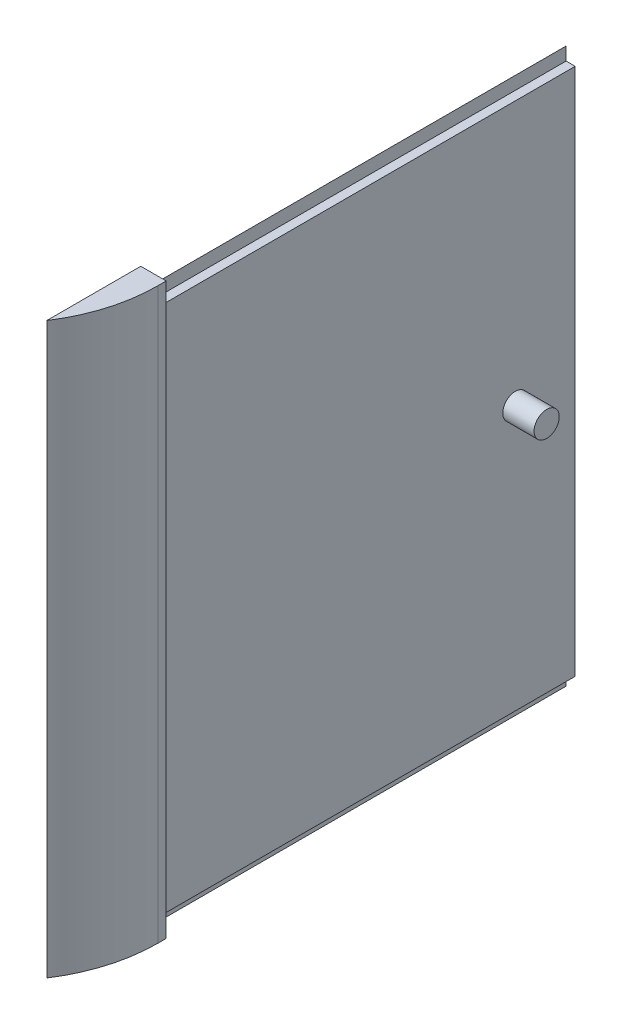
SolidWorks part; units mm, degrees
ref_plane "Front Plane" through (0, 0, 0) normal (0, 0, 1) x (1, 0, 0)
ref_plane "Top Plane" through (0, 0, 0) normal (0, 1, 0) x (1, 0, 0)
ref_plane "Right Plane" through (0, 0, 0) normal (1, 0, 0) x (0, 0, -1)
sketch "Sketch1" plane through (0, 0, 0) normal (0, 0, 1) x (1, 0, 0)
  line L0 (34.023, -148) -> (34.3868, -148) construction
  line L1 (37.6841, -12) -> (37.6841, -7.95) construction
  line L2 (37.6841, -7.95) -> (33.6841, -12) construction
  line L3 (33.6841, -147.5) -> (37.6841, -147.5) construction
  line L4 (37.1841, -12) -> (37.1841, -9.1678)
  line L5 (37.1841, -9.1678) -> (34.1841, -12.2053)
  line L6 (37.6841, -147.5) -> (39.5, -147.5)
  line L7 (39.5, -12.5) -> (39.5, -147.5)
  line L8 (37.6841, -148) -> (40, -148) construction
  line L9 (37.6841, -152.05) -> (37.6841, -148) construction
  line L11 (33.6841, -148) -> (37.6841, -152.05) construction
  line L12 (37.6841, -12) -> (40, -12) construction
  line L16 (40, -12) -> (40, -148) construction
  line L18 (33.6841, -12.5) -> (33.6841, -147.5) construction
  line L19 (37.6841, -12.5) -> (39.5, -12.5)
  line L20 (34.1841, -147.7947) -> (37.1841, -150.8322)
  line L21 (37.1841, -150.8322) -> (37.1841, -148)
  line L22 (34.1841, -12.2053) -> (34.1841, -147.7947)
  line L23 (37.1841, -147.5) -> (37.6841, -147.5)
  line L24 (37.6841, -12.5) -> (37.1841, -12.5)
  line L25 (34.0398, -147.6486) -> (37.1841, -150.8322) construction
  line L26 (33.6841, -148) -> (37.6841, -148) construction
  line L28 (37.1841, -148) -> (37.1841, -147.5)
  line L31 (37.1841, -9.1678) -> (34.0398, -12.3514) construction
  line L36 (37.1841, -12) -> (37.1841, -12.5)
  line L38 (34.1841, -12) -> (34.1841, -148) construction
  line L39 (33.6841, -12) -> (33.6841, -148) construction
  dimension "D1" = 4.05
  dimension "D2" = 4
  dimension "D3" = 0.5
extrude "Boss-Extrude1" add sketch "Sketch1" against normal blind 105
sketch "Sketch4" plane through (0, 0, 0) normal (0, 0, 1) x (1, 0, 0)
  line L1 (40, -152.75) -> (33.5, -152.75)
  line L3 (40, -7.25) -> (33.5, -7.25)
  line L4 (33.5, -152.75) -> (33.5, -7.25)
  line L5 (40, -80) -> (33.5, -80) construction
  line L6 (40, -7.25) -> (40, -80)
  line L7 (40, -80) -> (40, -152.75)
  dimension "D1" = 145.5
  dimension "D2" = 6.5
extrude "Boss-Extrude2" add sketch "Sketch4" along normal blind 24
fillet "Fillet1" radius 40 1 edges at (40, -80, 24)
sketch "Sketch5" plane through (39.5, 0, 0) normal (1, 0, 0) x (0, 0, -1)
  line L0 (89.7148, -12) -> (89.7148, -148) construction
  circle A0 centre (89.7148, -80) radius 3.2191
extrude "Boss-Extrude3" add sketch "Sketch5" along normal blind 8
